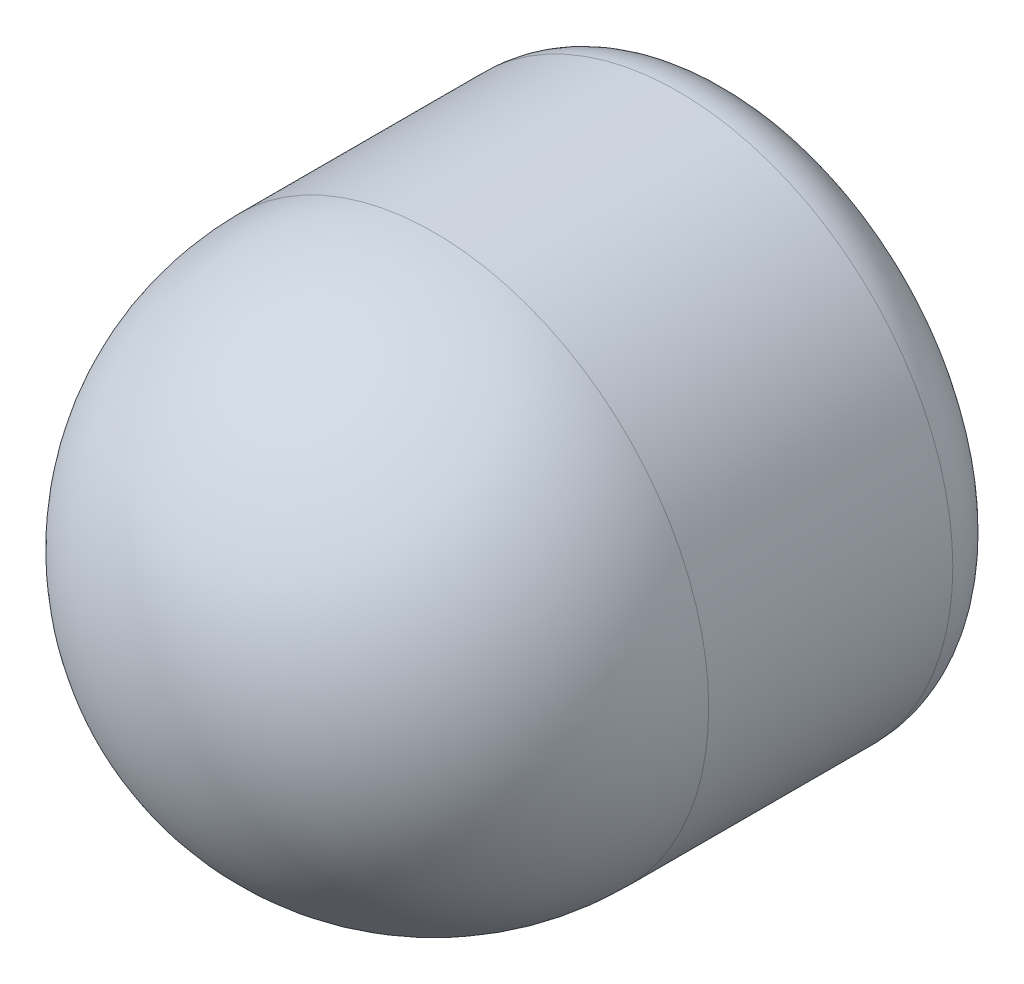
SolidWorks part; units mm, degrees
ref_plane "前视基准面" through (0, 0, 0) normal (0, 0, 1) x (1, 0, 0)
ref_plane "上视基准面" through (0, 0, 0) normal (0, 1, 0) x (1, 0, 0)
ref_plane "右视基准面" through (0, 0, 0) normal (1, 0, 0) x (0, 0, -1)
sketch "草图1" plane through (0, 0, 0) normal (0, 0, 1) x (1, 0, 0)
  line L0 (0, 9) -> (0, -9)
  arc A0 (0, -9) -> (0, 9) centre (0, 0) ccw
revolve "旋转1" add sketch "草图1" angle 360 about L0
sketch "草图3" plane through (0, 0, 0) normal (0, 0, 1) x (1, 0, 0)
  circle A0 centre (0, 0) radius 9
extrude "凸台-拉伸1" add sketch "草图3" against normal blind 10
sketch "草图2" plane through (0, 0, 0) normal (0, 0, 1) x (1, 0, 0)
  line L1 (-5.25, 5.25) -> (5.25, 5.25)
  line L2 (-5.25, 5.25) -> (-5.25, -5.25)
  line L3 (-5.25, -5.25) -> (5.25, -5.25)
  line L4 (5.25, 5.25) -> (5.25, -5.25)
  line L5 (-5.25, 5.25) -> (5.25, -5.25) construction
  line L6 (-5.25, -5.25) -> (5.25, 5.25) construction
  point P0 (0, 0)
  dimension "D1" = 10.5
  dimension "D2" = 10.5
extrude "切除-拉伸1" cut sketch "草图2" against normal blind 10
fillet "圆角1" radius 2 1 edges at (9, 0, -10)
